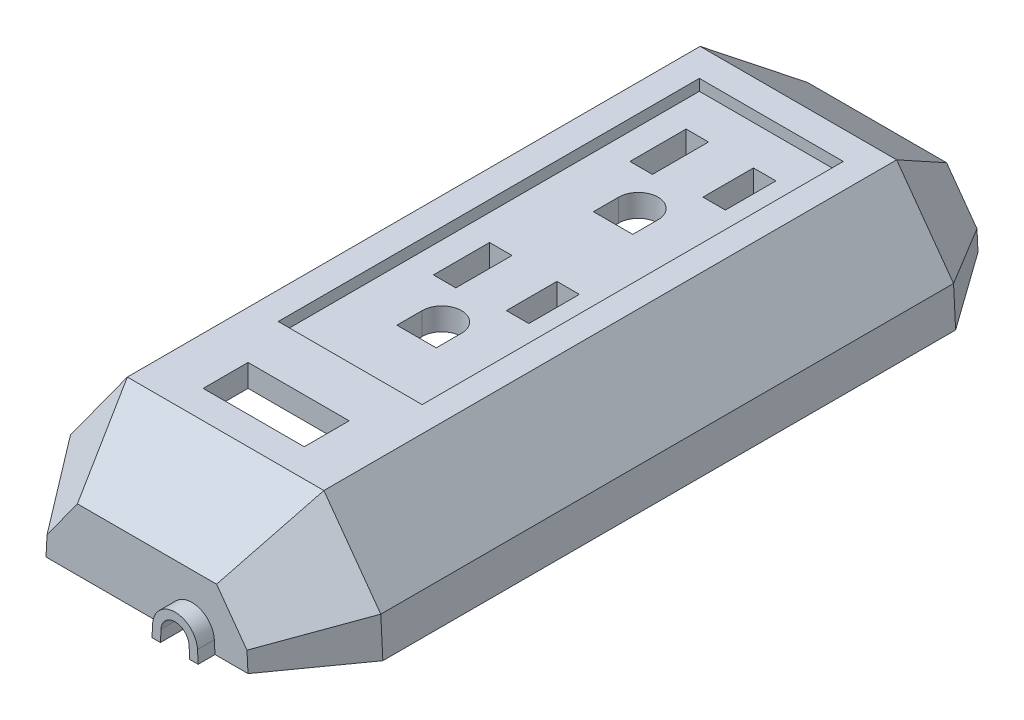
SolidWorks part; units mm, degrees
ref_plane "Front Plane" through (0, 0, 0) normal (0, 0, 1) x (1, 0, 0)
ref_plane "Top Plane" through (0, 0, 0) normal (0, 1, 0) x (1, 0, 0)
ref_plane "Right Plane" through (0, 0, 0) normal (1, 0, 0) x (0, 0, -1)
sketch "Sketch1" plane through (0, 0, 0) normal (0, 0, 1) x (1, 0, 0)
  line L0 (17.5, 21) -> (27.6331, 7)
  line L1 (-17.5, 21) -> (17.5, 21)
  line L2 (-27.6331, 7) -> (-28, 0)
  line L3 (-28, 0) -> (28, 0)
  line L4 (27.6331, 7) -> (28, 0)
  line L5 (-27.6331, 7) -> (-17.5, 21)
  line L6 (0, 0) -> (0, 21) construction
  dimension "D1" = 56
  dimension "D2" = 35
  dimension "D3" = 21
  dimension "D4" = 7
  dimension "D5" = 3
extrude "Extrude1" add sketch "Sketch1" along normal blind 130
chamfer "Chamfer1" distance 14 distance2 10 5 edges at (27.8166, 3.5, 130) (22.5666, 14, 130) (0, 21, 130) (-22.5666, 14, 130) (-27.8166, 3.5, 130) first distance on face at (27.8166, 3.5, 65) first distance on face at (22.5666, 14, 65) first distance on face at (0, 21, 65) first distance on face at (-22.5666, 14, 65) first distance on face at (-27.8166, 3.5, 65)
chamfer "Chamfer2" distance 10 distance2 14 5 edges at (-27.8166, 3.5, 0) (-22.5666, 14, 0) (0, 21, 0) (22.5666, 14, 0) (27.8166, 3.5, 0) first distance on face at (0, 9.3333, 0)
sketch "Sketch2" plane through (5.7452, -1.8948, 130) normal (0, 0, 1) x (1, 0, 0)
  line L1 (-23.7315, 1.8948) -> (12.2411, 1.8948) construction
  line L2 (-1.8555, 1.8948) -> (6.3651, 1.8948)
  line L3 (-1.8555, 1.8948) -> (-1.7397, 4.1042)
  line L4 (6.3651, 1.8948) -> (6.2493, 4.1042)
  line L5 (2.2548, 1.8948) -> (2.2548, 3.8948) construction
  arc A0 (6.2493, 4.1042) -> (-1.7397, 4.1042) centre (2.2548, 3.8948) ccw
  circle A1 centre (2.2548, 3.8948) radius 2 construction
  dimension "D1" = 4
  dimension "D3" = 6
  dimension "D5" = 4
  dimension "D2" = 3
  dimension "D4" = 8
extrude "Extrude2" add sketch "Sketch2" along normal blind 3
ref_plane "Plane1" through (0, 30, 0) normal (0, 1, 0) x (1, 0, 0)
sketch "Sketch3" plane through (3.4925, 30, 107.5782) normal (0, 1, 0) x (1, 0, 0)
  line L0 (-31.1257, -8.4218) -> (-31.1257, 93.5782) construction
  line L1 (9.5075, 88.5782) -> (-16.1257, 88.5782)
  line L2 (9.5075, 88.5782) -> (9.5075, 13.5782)
  line L3 (9.5075, 13.5782) -> (-16.1257, 13.5782)
  line L4 (-16.1257, 88.5782) -> (-16.1257, 13.5782)
  line L6 (24.5075, -8.4218) -> (24.5075, 93.5782) construction
  line L11 (-20.9925, 93.5782) -> (-31.1257, 93.5782) construction
  dimension "D1" = 75
  dimension "D2" = 15
  dimension "D3" = 15
  dimension "D4" = 80
extrude "Cut-Extrude1" cut sketch "Sketch3" against normal offset from surface (11 mm away) 2 up to face at (0, 21, 65) offset beyond the face yes
sketch "Sketch4" plane through (-3.0826, 30, 40.4689) normal (0, 1, 0) x (-1, 0, 0)
  line L1 (14.4174, -26.4689) -> (24.5505, -26.4689) construction
  line L3 (0.9174, -14.4689) -> (-7.0826, -14.4689) construction
  line L4 (-3.0826, 2.0311) -> (-3.0826, -14.4689) construction
  line L6 (-3.0826, 9.5311) -> (-3.0826, -90.4689) construction
  line L9 (-7.0826, -14.4689) -> (-7.0826, -5.4689)
  line L10 (-11.0826, -14.4689) -> (-7.0826, -14.4689)
  line L11 (-11.0826, -5.4689) -> (-11.0826, -14.4689)
  line L12 (-7.0826, -5.4689) -> (-11.0826, -5.4689)
  line L18 (4.9174, -14.4689) -> (4.9174, -4.4689)
  line L19 (0.9174, -14.4689) -> (4.9174, -14.4689)
  line L20 (0.9174, -4.4689) -> (0.9174, -14.4689)
  line L21 (4.9174, -4.4689) -> (0.9174, -4.4689)
  line L25 (-6.5826, 6.5311) -> (-6.5826, 2.0311)
  line L26 (0.4174, 6.5311) -> (-6.5826, 6.5311)
  line L27 (0.4174, 2.0311) -> (0.4174, 6.5311)
  arc A2 (-6.5826, 2.0311) -> (0.4174, 2.0311) centre (-3.0826, 2.0311) ccw
  dimension "D1" = 21
  dimension "D2" = 4
  dimension "D3" = 8
  dimension "D4" = 10
  dimension "D5" = 9
  dimension "D6" = 7
  dimension "D7" = 4.5
  dimension "D8" = 12
extrude "Cut-Extrude2" cut sketch "Sketch4" against normal offset from surface (15 mm away) 6 up to face at (0.1834, 21, 56.5) offset beyond the face yes
pattern_linear "LPattern1" count 2 spacing 35 along (0, 0, 1) of "Cut-Extrude2"
sketch "Sketch5" plane through (0.7926, 30, 213.5131) normal (0, 1, 0) x (1, 0, 0)
  line L0 (-0.7926, 102.5131) -> (-0.7926, 110.5131) construction
  line L1 (-9.7926, 102.5131) -> (8.2074, 102.5131)
  line L2 (-9.7926, 102.5131) -> (-9.7926, 110.5131)
  line L3 (-9.7926, 110.5131) -> (8.2074, 110.5131)
  line L4 (8.2074, 102.5131) -> (8.2074, 110.5131)
  line L5 (-28.4257, 97.5131) -> (-18.2926, 97.5131) construction
  line L8 (-0.7926, 163.5131) -> (-0.7926, 263.5131) construction
  dimension "D1" = 5
  dimension "D2" = 8
  dimension "D3" = 18
extrude "Cut-Extrude3" cut sketch "Sketch5" against normal offset from surface (13 mm away) 4 up to face at (0.1834, 21, 56.5) offset beyond the face yes
shell "Shell1" thickness 1.5 removed face at (6, 15, 30.5) removed face at (-6, 15, 31) removed face at (0, 15, 43.875) removed face at (6, 15, 65.5) removed face at (-6, 15, 66) removed face at (0, 15, 78.875) removed face at (0, 17, 107) removed face at (1.5103, 0, 87.4167) removed face at (8, 2.0523, 133)
